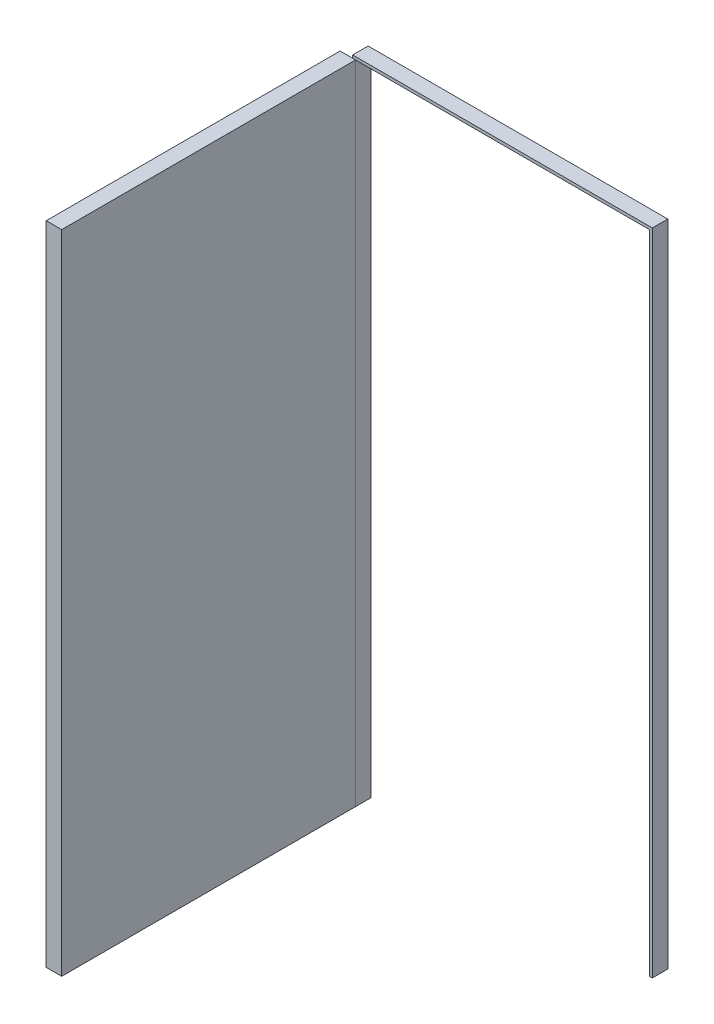
SolidWorks part; units mm, degrees
ref_plane "Front" through (0, 0, 0) normal (0, 0, 1) x (1, 0, 0)
ref_plane "Top" through (0, 0, 0) normal (0, 1, 0) x (1, 0, 0)
ref_plane "Right" through (0, 0, 0) normal (1, 0, 0) x (0, 0, -1)
sketch "Sketch1" plane through (0, 0, 0) normal (0, 0, 1) x (1, 0, 0)
  line L0 (965.2, 2114.55) -> (965.2, -2133.6)
  line L1 (-984.25, 2133.6) -> (984.25, 2133.6)
  line L2 (-984.25, 2133.6) -> (-984.25, -2133.6)
  line L3 (-984.25, -2133.6) -> (984.25, -2133.6) construction
  line L4 (984.25, 2133.6) -> (984.25, -2133.6)
  line L5 (-984.25, 2133.6) -> (984.25, -2133.6) construction
  line L6 (-984.25, -2133.6) -> (984.25, 2133.6) construction
  line L7 (-965.2, 2114.55) -> (965.2, 2114.55)
  line L8 (-965.2, 2114.55) -> (-965.2, -2133.6)
  line L9 (-984.25, -2133.6) -> (-965.2, -2133.6)
  line L10 (965.2, -2133.6) -> (984.25, -2133.6)
  point P0 (0, 0)
  dimension "D1" = 4267.2
  dimension "D3" = 1930.4
  dimension "D2" = 19.05
extrude "Boss-Extrude1" add sketch "Sketch1" along normal blind 101.6
sketch "Sketch2" plane through (0, -2133.6, 0) normal (0, -1, 0) x (1, 0, 0)
  line L0 (-965.2, 101.6) -> (-965.2, 2032)
  line L1 (-965.2, 2032) -> (-1066.8, 2032)
  line L2 (-1066.8, 2032) -> (-1066.8, 101.6)
  line L3 (-1066.8, 101.6) -> (-965.2, 101.6)
  line L4 (-965.2, 0) -> (965.2, 0) construction
  dimension "D1" = 101.6
  dimension "D2" = 90
extrude "Boss-Extrude2" add sketch "Sketch2" against normal up to surface (4248.15 mm away) separate body up to face at (0, 2114.55, 50.8)
sketch "Sketch3" plane through (0, 0, 2032) normal (0, 0, 1) x (1, 0, 0)
  line L0 (-1066.8, 2114.55) -> (-1066.8, -2133.6) construction
  line L1 (-1066.8, -787.4) -> (-1193.8, -787.4)
  line L2 (-1066.8, -787.4) -> (-1066.8, -838.2)
  line L3 (-1066.8, -1117.6) -> (-1193.8, -1117.6)
  line L4 (-1193.8, -787.4) -> (-1193.8, -1117.6)
  line L5 (-1066.8, -1066.8) -> (-1066.8, -1117.6)
  line L6 (-1066.8, -838.2) -> (-1143, -838.2)
  line L8 (-1066.8, -1066.8) -> (-1143, -1066.8)
  line L9 (-1143, -838.2) -> (-1143, -1066.8)
  line L10 (-1143, -838.2) -> (-1193.8, -838.2) construction
  line L11 (-1143, -838.2) -> (-1143, -787.4) construction
  line L12 (-1143, -1066.8) -> (-1143, -1117.6) construction
  line L13 (-965.2, -2133.6) -> (-1066.8, -2133.6) construction
  dimension "D1" = 50.8
  dimension "D2" = 1016
  dimension "D3" = 76.2
  dimension "D4" = 330.2
extrude "Boss-Extrude3" add sketch "Sketch3" along normal blind 38.1 from offset 228.6 offset against normal yes
fillet "Fillet1" radius 38.1 2 edges at (-1193.8, -1117.6, 1822.45) (-1193.8, -787.4, 1822.45)
fillet "Fillet2" radius 12.7 2 edges at (-1143, -1066.8, 1822.45) (-1143, -838.2, 1822.45)
fillet "Fillet3" radius 12.7 20 edges at (-1098.55, -1066.8, 1803.4) (-1139.2803, -1063.0803, 1803.4) (-1143, -952.5, 1803.4) (-1139.2803, -841.9197, 1803.4) (-1098.55, -838.2, 1803.4) (-1111.25, -787.4, 1803.4) (-1182.6408, -798.5592, 1803.4) (-1193.8, -952.5, 1803.4) (-1182.6408, -1106.4408, 1803.4) (-1111.25, -1117.6, 1803.4) (-1182.6408, -798.5592, 1841.5) (-1111.25, -787.4, 1841.5) (-1098.55, -838.2, 1841.5) (-1139.2803, -841.9197, 1841.5) (-1143, -952.5, 1841.5) (-1139.2803, -1063.0803, 1841.5) (-1098.55, -1066.8, 1841.5) (-1111.25, -1117.6, 1841.5) (-1182.6408, -1106.4408, 1841.5) (-1193.8, -952.5, 1841.5)
